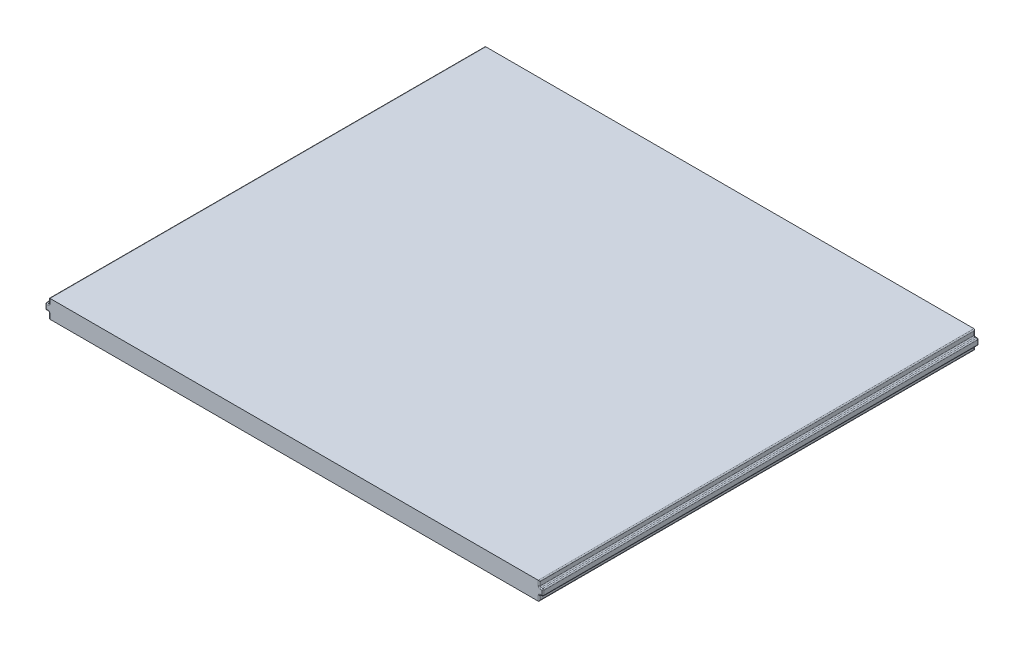
SolidWorks part; units mm, degrees
ref_plane "Front Plane" through (0, 0, 0) normal (0, 0, 1) x (1, 0, 0)
ref_plane "Top Plane" through (0, 0, 0) normal (0, 1, 0) x (1, 0, 0)
ref_plane "Right Plane" through (0, 0, 0) normal (1, 0, 0) x (0, 0, -1)
sketch "Sketch1" plane through (0, 0, 0) normal (0, 1, 0) x (1, 0, 0)
  line L1 (1433.9721, 1066.4463) -> (1568.9721, 1066.4463)
  line L2 (1433.9721, 1066.4463) -> (1433.9721, 946.4463)
  line L3 (1433.9721, 946.4463) -> (1568.9721, 946.4463)
  line L4 (1568.9721, 1066.4463) -> (1568.9721, 946.4463)
  dimension "D1" = 135
  dimension "D2" = 120
extrude "Boss-Extrude1" add sketch "Sketch1" along normal blind 5
sketch "Sketch2" plane through (1568.9721, 0, 0) normal (1, 0, 0) x (0, 0, -1)
  line L1 (946.4463, 5) -> (946.4463, 0) construction
  line L2 (946.4463, 3.4) -> (1066.4463, 3.4)
  line L3 (946.4463, 3.4) -> (946.4463, 1.65)
  line L4 (946.4463, 1.65) -> (1066.4463, 1.65)
  line L5 (1066.4463, 3.4) -> (1066.4463, 1.65)
  line L6 (1066.4463, 5) -> (1066.4463, 0) construction
  line L7 (946.4463, 0) -> (1066.4463, 0) construction
  dimension "D1" = 1.75
  dimension "D2" = 1.65
extrude "Boss-Extrude2" add sketch "Sketch2" along normal blind 1
ref_plane "Plane1" through (1501.4721, 0, 0) normal (-1, 0, 0) x (0, 0, 1)
mirror "Mirror1" about plane through (1501.4721, 0, 0) normal (-1, 0, 0) of "Boss-Extrude2"
fillet "Fillet1" radius 0.3 32 edges at (1569.4721, 1.65, -1066.4463) (1569.4721, 1.65, -946.4463) (1569.4721, 3.4, -946.4463) (1569.4721, 3.4, -1066.4463) (1568.9721, 0.825, -1066.4463) (1568.9721, 0, -1006.4463) (1568.9721, 0.825, -946.4463) (1568.9721, 1.65, -1006.4463) (1569.9721, 3.4, -1006.4463) (1569.9721, 2.525, -1066.4463) (1569.9721, 1.65, -1006.4463) (1569.9721, 2.525, -946.4463) (1568.9721, 4.2, -946.4463) (1568.9721, 5, -1006.4463) (1568.9721, 4.2, -1066.4463) (1568.9721, 3.4, -1006.4463) (1433.4721, 1.65, -1066.4463) (1433.4721, 1.65, -946.4463) (1433.4721, 3.4, -946.4463) (1433.4721, 3.4, -1066.4463) (1433.9721, 0, -1006.4463) (1433.9721, 0.825, -1066.4463) (1433.9721, 1.65, -1006.4463) (1433.9721, 0.825, -946.4463) (1433.9721, 5, -1006.4463) (1433.9721, 4.2, -946.4463) (1433.9721, 3.4, -1006.4463) (1433.9721, 4.2, -1066.4463) (1432.9721, 1.65, -1006.4463) (1432.9721, 2.525, -1066.4463) (1432.9721, 3.4, -1006.4463) (1432.9721, 2.525, -946.4463)
